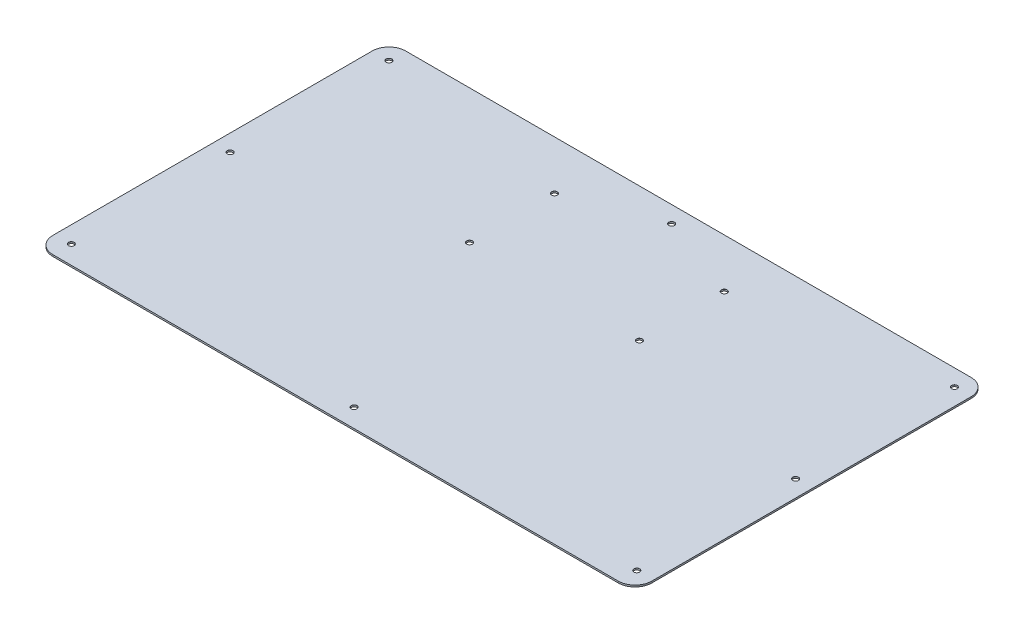
SolidWorks part; units mm, degrees
ref_plane "Front Plane" through (0, 0, 0) normal (0, 0, 1) x (1, 0, 0)
ref_plane "Top Plane" through (0, 0, 0) normal (0, 1, 0) x (1, 0, 0)
ref_plane "Right Plane" through (0, 0, 0) normal (1, 0, 0) x (0, 0, -1)
sketch "Sketch1" plane through (0, 0, 0) normal (0, 1, 0) x (1, 0, 0)
  line L1 (-179.135, 105.525) -> (179.135, 105.525)
  line L2 (-179.135, 105.525) -> (-179.135, -105.525)
  line L3 (-179.135, -105.525) -> (179.135, -105.525)
  line L4 (179.135, 105.525) -> (179.135, -105.525)
  line L5 (-179.135, 105.525) -> (179.135, -105.525) construction
  line L6 (-179.135, -105.525) -> (179.135, 105.525) construction
  point P0 (0, 0)
  dimension "D1" = 358.27
  dimension "D2" = 211.05
extrude "Boss-Extrude1" add sketch "Sketch1" along normal blind 1
fillet "Fillet1" radius 10 4 edges at (-179.135, 0.5, -105.525) (-179.135, 0.5, 105.525) (179.135, 0.5, -105.525) (179.135, 0.5, 105.525)
hole_wizard "M3 Clearance Hole1" positions "Sketch2" profile "Sketch3" hole size "M3" standard "ANSI Metric" end condition through all
sketch "Sketch2" plane through (0, 1, 0) normal (0, 1, 0) x (1, 0, 0)
  point P0 (169.135, 0.525)
  point P3 (169.135, -94.475)
  point P6 (169.135, 95.525)
  point P9 (0, 95.525)
  point P12 (-169.135, 95.525)
  point P15 (-169.135, 0.525)
  point P18 (-169.135, -94.475)
  point P21 (0, -94.475)
sketch "Sketch3" plane through (169.135, 1, -0.525) normal (1, 0, 0) x (0, 0, 1)
  line L0 (0, 0) -> (0, 1)
  line L1 (0, 1) -> (1.7, 1)
  line L2 (1.7, 1) -> (1.7, 0.025)
  line L3 (1.7, 0.025) -> (1.725, 0)
  line L5 (1.725, 0) -> (0, 0)
  line L6 (-1.7, 0.025) -> (-1.725, 0) construction
  line L11 (0, -6.35) -> (0, 107.95) construction
  dimension "Thru Hole Dia." = 3.4
  dimension "Thru Hole Depth" = 1
  dimension "Near C'Sink Dia." = 3.45
  dimension "Near C'Sink Angle" = 90
hole_wizard "M3 Clearance Hole3" positions "Sketch4" profile "Sketch5" hole size "M3" standard "ANSI Metric" end condition through all
sketch "Sketch4" plane through (0, 1, 0) normal (0, 1, 0) x (1, 0, 0)
  line L0 (0, 0) -> (0, 50.8) construction
  line L3 (-50.8, 25.4) -> (50.8, 25.4)
  line L4 (-50.8, 25.4) -> (-50.8, 76.2)
  line L5 (-50.8, 76.2) -> (50.8, 76.2)
  line L6 (50.8, 25.4) -> (50.8, 76.2)
  line L7 (-50.8, 25.4) -> (50.8, 76.2) construction
  line L8 (-50.8, 76.2) -> (50.8, 25.4) construction
  point P7 (50.8, 76.2)
  point P106 (-50.8, 25.4)
  point P107 (-50.8, 76.2)
  point P108 (50.8, 25.4)
  point P120 (0, 41.4965)
  dimension "D1" = 50.8
  dimension "D2" = 101.6
  dimension "D3" = 50.8
sketch "Sketch5" plane through (50.8, 1, -25.4) normal (1, 0, 0) x (0, 0, 1)
  line L0 (0, 0) -> (0, 1)
  line L1 (0, 1) -> (1.7, 1)
  line L2 (1.7, 1) -> (1.7, 0.025)
  line L3 (1.7, 0.025) -> (1.725, 0)
  line L5 (1.725, 0) -> (0, 0)
  line L6 (-1.7, 0.025) -> (-1.725, 0) construction
  line L11 (0, -6.35) -> (0, 107.95) construction
  dimension "Thru Hole Dia." = 3.4
  dimension "Thru Hole Depth" = 1
  dimension "Near C'Sink Dia." = 3.45
  dimension "Near C'Sink Angle" = 90
